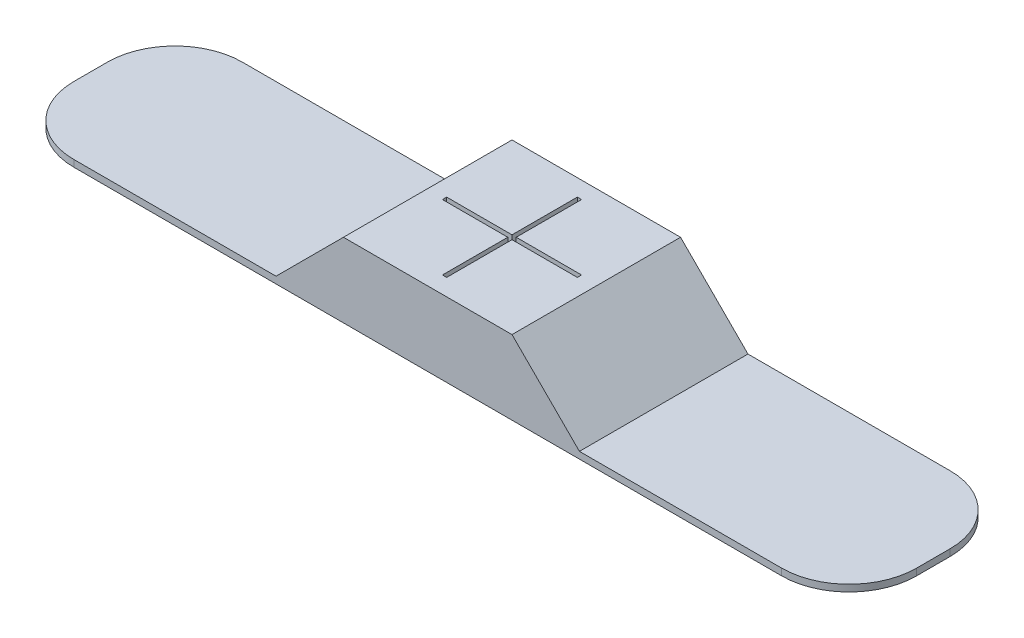
SolidWorks part; units mm, degrees
ref_plane "Front" through (0, 0, 0) normal (0, 0, 1) x (1, 0, 0)
ref_plane "Top" through (0, 0, 0) normal (0, 1, 0) x (1, 0, 0)
ref_plane "Right" through (0, 0, 0) normal (1, 0, 0) x (0, 0, -1)
sketch "Sketch1" plane through (0, 0, 0) normal (0, 1, 0) x (1, 0, 0)
  line L0 (-0.7937, 25.4) -> (0.7938, 25.4)
  line L1 (-31.75, -31.75) -> (31.75, -31.75)
  line L2 (-31.75, -31.75) -> (-31.75, 31.75)
  line L3 (-31.75, 31.75) -> (31.75, 31.75)
  line L4 (31.75, -31.75) -> (31.75, 31.75)
  line L5 (0, 31.75) -> (0, -31.75) construction
  line L6 (-31.75, 0) -> (31.75, 0) construction
  line L11 (0, 25.4) -> (0, -25.4) construction
  line L12 (-25.4, 0) -> (25.4, 0) construction
  line L13 (0.7938, 25.4) -> (0.7938, -25.4) construction
  line L14 (-0.7937, -25.4) -> (-0.7937, 25.4) construction
  line L15 (-25.4, 0.7938) -> (25.4, 0.7937) construction
  line L16 (25.4, -0.7938) -> (-25.4, -0.7937) construction
  line L17 (0.7938, 25.4) -> (0.7937, -25.4) construction
  line L18 (-0.7938, -25.4) -> (-0.7937, 25.4) construction
  line L19 (25.4, -0.7938) -> (-25.4, -0.7937) construction
  line L20 (-25.4, 0.7938) -> (25.4, 0.7937) construction
  line L21 (25.4, 0.7937) -> (25.4, -0.7938)
  line L22 (25.4, -0.7938) -> (0.7938, -0.7938)
  line L23 (25.4, 0.7937) -> (0.7938, 0.7938)
  line L24 (-0.7938, -25.4) -> (-0.7938, -0.7938)
  line L25 (0.7937, -25.4) -> (0.7938, -0.7938)
  line L26 (0.7937, -25.4) -> (-0.7938, -25.4)
  line L27 (-25.4, 0.7938) -> (-0.7937, 0.7938)
  line L28 (-25.4, -0.7937) -> (-0.7938, -0.7938)
  line L29 (-25.4, -0.7937) -> (-25.4, 0.7938)
  line L30 (0.7938, 25.4) -> (0.7938, 0.7938)
  line L31 (-0.7937, 25.4) -> (-0.7937, 0.7938)
  line L32 (-0.7937, 25.4) -> (0.7938, 25.4)
  line L34 (31.75, 31.75) -> (158.75, 31.75)
  line L35 (31.75, 31.75) -> (31.75, -31.75)
  line L36 (31.75, -31.75) -> (158.75, -31.75)
  line L37 (158.75, 31.75) -> (158.75, -31.75)
  line L38 (31.75, 31.75) -> (158.75, -31.75) construction
  line L39 (31.75, -31.75) -> (158.75, 31.75) construction
  line L40 (-31.75, 31.75) -> (-158.75, 31.75)
  line L41 (-31.75, 31.75) -> (-31.75, -31.75)
  line L42 (-31.75, -31.75) -> (-158.75, -31.75)
  line L43 (-158.75, 31.75) -> (-158.75, -31.75)
  line L44 (-31.75, 31.75) -> (-158.75, -31.75) construction
  line L45 (-31.75, -31.75) -> (-158.75, 31.75) construction
  point P0 (0, 0)
  point P4 (0, 0)
  point P11 (0, 25.4)
  point P14 (95.25, 0)
  point P28 (0, 0)
  point P36 (-95.25, 0)
  point P40 (0, 0)
  dimension "D1" = 63.5
  dimension "D2" = 63.5
  dimension "D3" = 4
  dimension "D4" = 127
  dimension "D5" = 1.5875
  dimension "D7" = 127
  dimension "D6" = 4
extrude "Boss-Extrude1" add sketch "Sketch1" along normal blind 25.4 contours L1 L4 L3 L2 L31 L0 L30 L23 L21 L22 L25 L26 L24 L28 L29 L27 region at (-30.852, 0, 0)
extrude "Boss-Extrude2" add sketch "Sketch1<3>" against normal blind 2.54 contours L1 L4 L3 L2 L31 L0 L30 L23 L21 L22 L25 L26 L24 L28 L29 L27 | L31 L27 L29 L28 L24 L26 L25 L22 L21 L23 L30 L32 region at (-30.852, 0, 0)
sketch "Sketch1<3>" plane through (0, 0, 0) normal (0, 1, 0) x (1, 0, 0) same geometry as "Sketch1"
extrude "Boss-Extrude3" add sketch "Sketch1<4>" against normal blind 2.54 contours L37 L34 L4 L36 | L40 L43 L42 L2 region at (-95.25, 0, 0) region at (95.25, 0, 0)
sketch "Sketch1<4>" plane through (0, 0, 0) normal (0, 1, 0) x (1, 0, 0) same geometry as "Sketch1"
chamfer "Chamfer2" distance 25.4 angle 45 2 edges at (31.75, 0, 0) (-31.75, 0, 0)
fillet "Fillet1" radius 25.4 4 edges at (-158.75, -1.27, 31.75) (-158.75, -1.27, -31.75) (158.75, -1.27, -31.75) (158.75, -1.27, 31.75)
